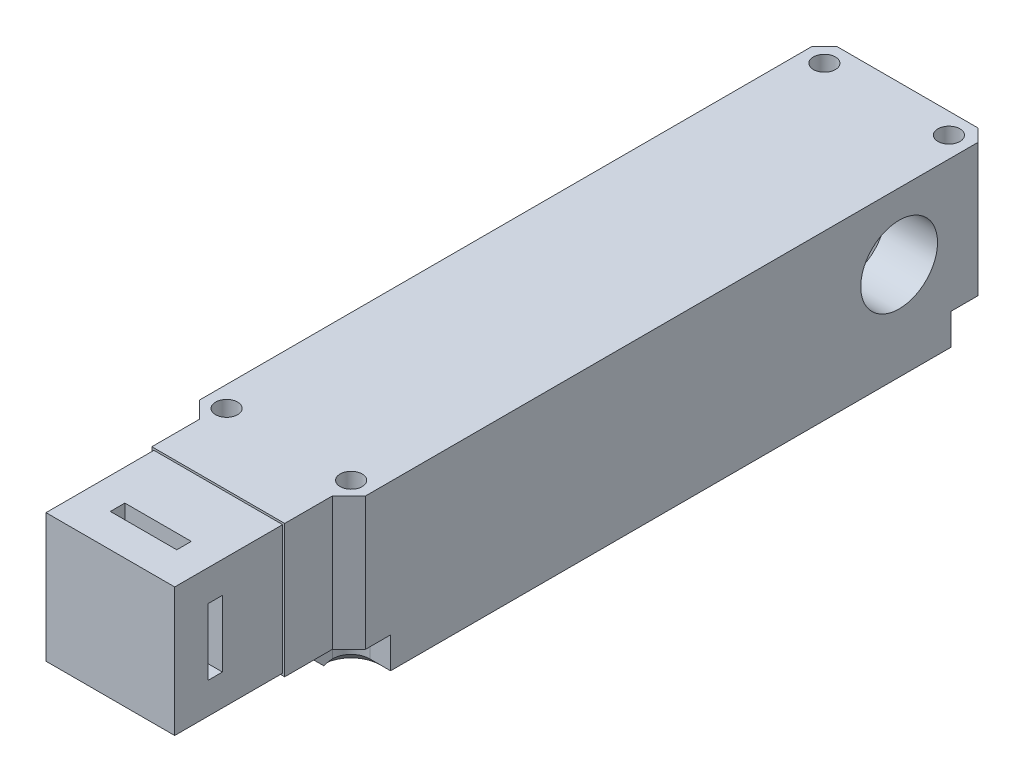
SolidWorks part; units mm, degrees
material "Kunststoff schwarz"
ref_plane "Front" through (0, 0, 0) normal (0, 0, 1) x (1, 0, 0)
ref_plane "Top" through (0, 0, 0) normal (0, 1, 0) x (1, 0, 0)
ref_plane "Right" through (0, 0, 0) normal (1, 0, 0) x (0, 0, -1)
sketch "Skizze1" plane through (0, 0, 0) normal (0, 1, 0) x (1, 0, 0)
  line L0 (16, -17) -> (-16, -17)
  line L1 (-16, -17) -> (-16, -5.5)
  line L2 (-16, -5.5) -> (-20, -1.5)
  line L3 (-20, -1.5) -> (-20, 146)
  line L4 (-20, 146) -> (-17, 149)
  line L5 (-17, 149) -> (17, 149)
  line L6 (17, 149) -> (20, 146)
  line L7 (20, 146) -> (20, -1.5)
  line L8 (20, -1.5) -> (16, -5.5)
  line L9 (16, -5.5) -> (16, -17)
  line L10 (0, -17) -> (0, 149) construction
  line L11 (15, 0) -> (-15, 0) construction
  circle A0 centre (15, 0) radius 2.65
  circle A1 centre (-15, 0) radius 2.65
  circle A2 centre (-15, 144) radius 2.65
  circle A3 centre (15, 144) radius 2.65
  dimension "D5" = 30
  dimension "D6" = 5
  dimension "D7" = 144
  dimension "D8" = 5.3
  dimension "D1" = 166
  dimension "D2" = 4
  dimension "D3" = 32
  dimension "D4" = 40
  dimension "D9" = 147.5
  dimension "D10" = 3
extrude "Aufsatz-Linear austragen1" add sketch "Skizze1" against normal blind 32 separate body
sketch "Skizze2" plane through (0, 0, 17) normal (0, 0, 1) x (1, 0, 0)
  line L0 (16, -32) -> (-16, 0) construction
  line L2 (15.5, -0.5) -> (-15.5, -0.5)
  line L3 (15.5, -0.5) -> (15.5, -31.5)
  line L4 (15.5, -31.5) -> (-15.5, -31.5)
  line L5 (-15.5, -0.5) -> (-15.5, -31.5)
  line L6 (15.5, -0.5) -> (-15.5, -31.5) construction
  line L7 (15.5, -31.5) -> (-15.5, -0.5) construction
  point P4 (0, -16)
  dimension "D1" = 31
extrude "Aufsatz-Linear austragen2" add sketch "Skizze2" along normal blind 26
sketch "Skizze3" plane through (0, -32, 0) normal (0, -1, 0) x (1, 0, 0)
  line L0 (20, -4.5) -> (15, -4.5)
  line L1 (20, 1.5) -> (20, -146) construction
  line L2 (10.5, 0) -> (10.5, 4.5)
  line L3 (10.5, 4.5) -> (-10.5, 4.5)
  line L4 (-10.5, 4.5) -> (-10.5, 0)
  line L5 (-15, -4.5) -> (-20, -4.5)
  line L6 (-20, -146) -> (-20, 1.5) construction
  line L7 (-20, -4.5) -> (-20, -139.5)
  line L8 (-20, -139.5) -> (-15, -139.5)
  line L9 (-10.5, -144) -> (-10.5, -149)
  line L10 (17, -149) -> (-17, -149) construction
  line L11 (-10.5, -149) -> (10.5, -149)
  line L12 (10.5, -149) -> (10.5, -144)
  line L13 (15, -139.5) -> (20, -139.5)
  line L14 (20, -139.5) -> (20, -4.5)
  arc A0 (15, -4.5) -> (10.5, 0) centre (15, 0) cw
  arc A1 (-10.5, 0) -> (-15, -4.5) centre (-15, 0) cw
  arc A2 (-15, -139.5) -> (-10.5, -144) centre (-15, -144) cw
  arc A3 (10.5, -144) -> (15, -139.5) centre (15, -144) cw
  circle A5 centre (15, 0) radius 2.65 construction
  circle A6 centre (15, -144) radius 2.65 construction
  dimension "D2" = 4.5
  dimension "D3" = 153.5
extrude "Aufsatz-Linear austragen3" add sketch "Skizze3" along normal blind 10
chamfer "Fase2" distance 4.5 angle 45 2 edges at (0, -42, 4.5) (0, -42, -149)
chamfer "Fase1" distance 2.5 angle 45 12 edges at (17.5, -42, -139.5) (11.818, -42, -140.818) (10.5, -42, -144.25) (-10.5, -42, -144.25) (-11.818, -42, -140.818) (-17.5, -42, -139.5) (-20, -42, -72) (-17.5, -42, -4.5) (-11.818, -42, -3.182) (11.818, -42, -3.182) (17.5, -42, -4.5) (20, -42, -72)
hole_wizard "M20x1.5 Gewindebohrung1" positions "Skizze4" profile "Skizze5" tap size "M20x1.5" standard "Gabler-Normteile"
sketch "Skizze4" plane through (0, 0, -149) normal (0, 0, -1) x (-1, 0, 0)
  line L0 (-17, 0) -> (17, 0) construction
  point P0 (0, -16)
  dimension "D1" = 16
sketch "Skizze5" plane through (0, -16, -149) normal (1, 0, 0) x (0, 1, 0)
  line L0 (0, 0) -> (0, 13.558)
  line L1 (0, 13.558) -> (9.25, 8)
  line L2 (9.25, 8) -> (9.25, 0)
  line L5 (9.25, 0) -> (0, 0)
  line L10 (0, 13.558) -> (-9.25, 8) construction
  line L11 (0, -6.35) -> (0, 107.95) construction
  dimension "Bohrerdurchmesser" = 18.5
  dimension "Bohrungstiefe" = 8
  dimension "Spitzenwinkel" = 118
cosmetic thread "Bohrungsgewinde1" parameters "D1"=5, "D2"=20
hole_wizard "M20x1.5 Gewindebohrung2" positions "Skizze6" profile "Skizze7" tap size "M20x1.5" standard "Gabler-Normteile"
sketch "Skizze6" plane through (-20, 0, 0) normal (-1, 0, 0) x (0, 0, 1)
  line L0 (-146, 0) -> (1.5, 0) construction
  line L1 (-149, -32) -> (-149, 0) construction
  point P0 (-127, -16)
  dimension "D1" = 16
  dimension "D2" = 22
sketch "Skizze7" plane through (-20, -16, -127) normal (0, 1, 0) x (0, 0, 1)
  line L0 (0, 0) -> (0, 18.058)
  line L1 (0, 18.058) -> (9.25, 12.5)
  line L2 (9.25, 12.5) -> (9.25, 0)
  line L5 (9.25, 0) -> (0, 0)
  line L10 (0, 18.058) -> (-9.25, 12.5) construction
  line L11 (0, -6.35) -> (0, 107.95) construction
  dimension "Bohrerdurchmesser" = 18.5
  dimension "Bohrungstiefe" = 12.5
  dimension "Spitzenwinkel" = 118
cosmetic thread "Bohrungsgewinde2" parameters "D1"=5, "D2"=20
hole_wizard "M20x1.5 Gewindebohrung3" positions "Skizze8" profile "Skizze9" tap size "M20x1.5" standard "Gabler-Normteile"
sketch "Skizze8" plane through (20, 0, 0) normal (1, 0, 0) x (0, 0, -1)
  circle A0 centre (127, -16) radius 9.25 construction
  point P0 (127, -16)
sketch "Skizze9" plane through (20, -16, -127) normal (0, 1, 0) x (0, 0, -1)
  line L0 (0, 0) -> (0, 18.058)
  line L1 (0, 18.058) -> (9.25, 12.5)
  line L2 (9.25, 12.5) -> (9.25, 0)
  line L5 (9.25, 0) -> (0, 0)
  line L10 (0, 18.058) -> (-9.25, 12.5) construction
  line L11 (0, -6.35) -> (0, 107.95) construction
  dimension "Bohrerdurchmesser" = 18.5
  dimension "Bohrungstiefe" = 12.5
  dimension "Spitzenwinkel" = 118
cosmetic thread "Bohrungsgewinde3" parameters "D1"=5, "D2"=20
ref_plane "Ebene1" through (0, 0, 35) normal (0, 0, 1) x (1, 0, 0)
sketch "Skizze10" plane through (0, 0, 35) normal (0, 0, 1) x (1, 0, 0)
  line L0 (15.5, -31.5) -> (15.5, -0.5) construction
  line L1 (15.5, -8) -> (9.5, -8)
  line L2 (15.5, -8) -> (15.5, -24)
  line L3 (15.5, -24) -> (9.5, -24)
  line L4 (9.5, -8) -> (9.5, -24)
  line L5 (8, -31.5) -> (-8, -31.5)
  line L6 (8, -31.5) -> (8, -25.5)
  line L7 (8, -25.5) -> (-8, -25.5)
  line L8 (-8, -31.5) -> (-8, -25.5)
  line L9 (-15.5, -24) -> (-9.5, -24)
  line L10 (-15.5, -24) -> (-15.5, -8)
  line L11 (-15.5, -8) -> (-9.5, -8)
  line L12 (-9.5, -24) -> (-9.5, -8)
  line L13 (8, -0.5) -> (-8, -0.5)
  line L14 (8, -0.5) -> (8, -6.5)
  line L15 (8, -6.5) -> (-8, -6.5)
  line L16 (-8, -0.5) -> (-8, -6.5)
  line L17 (-15.5, -31.5) -> (15.5, -31.5) construction
  line L18 (-15.5, -0.5) -> (-15.5, -31.5) construction
  line L19 (15.5, -0.5) -> (-15.5, -0.5) construction
  point P24 (0, -31.5)
  point P25 (15.5, -16)
  point P26 (0, -0.5)
  point P27 (-15.5, -16)
  dimension "D1" = 16
  dimension "D2" = 6
extrude "Schnitt-Linear austragen1" cut sketch "Skizze10" against normal blind 3.5
